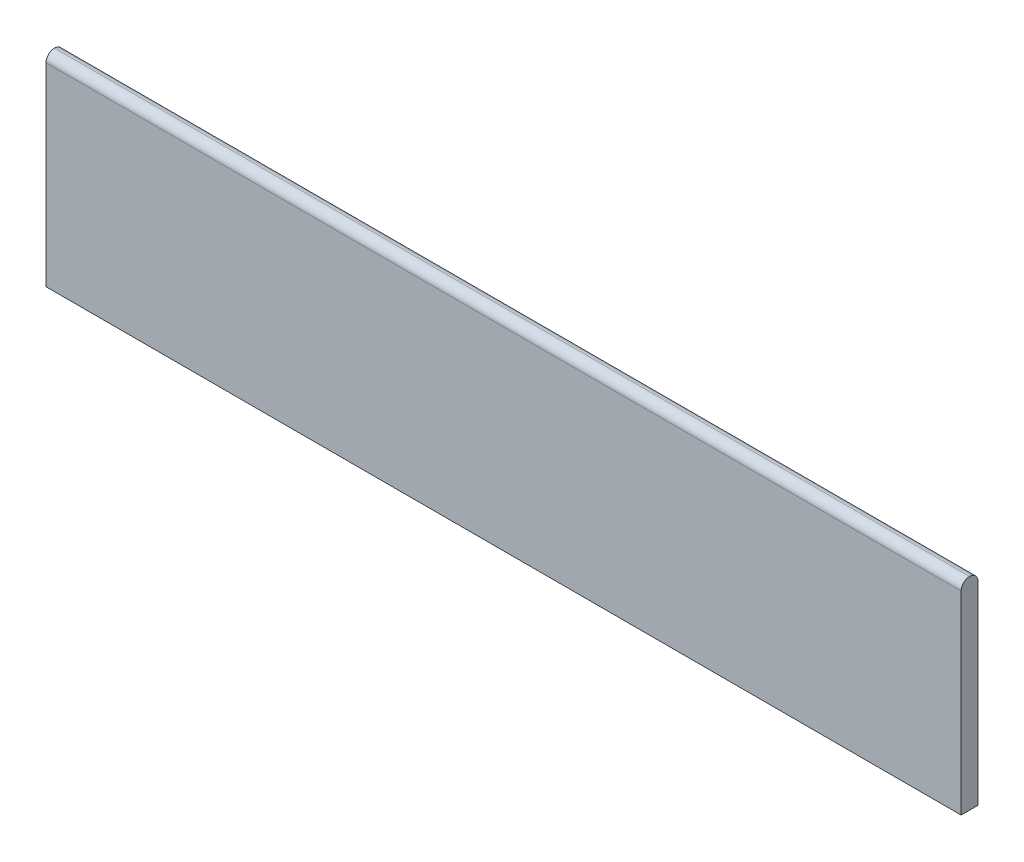
SolidWorks part; units mm, degrees
ref_plane "前视基准面" through (0, 0, 0) normal (0, 0, 1) x (1, 0, 0)
ref_plane "上视基准面" through (0, 0, 0) normal (0, 1, 0) x (1, 0, 0)
ref_plane "右视基准面" through (0, 0, 0) normal (1, 0, 0) x (0, 0, -1)
sketch "草图1" plane through (0, 0, 0) normal (0, 0, 1) x (1, 0, 0)
  line L1 (0, 0) -> (678, 0)
  line L2 (0, 0) -> (0, 150)
  line L3 (0, 150) -> (678, 150)
  line L4 (678, 0) -> (678, 150)
extrude "凸台-拉伸1" add sketch "草图1" along normal blind 12.5
fillet "圆角1" radius 6.25 1 edges at (339, 150, 12.5)
fillet "圆角2" radius 6.25 1 edges at (339, 150, 0)
